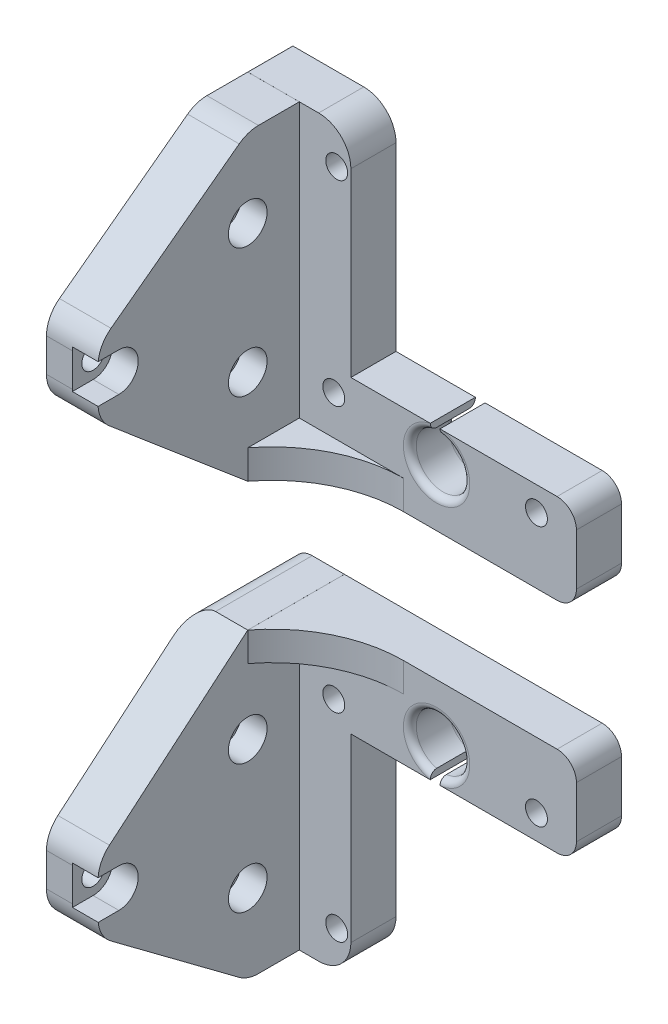
SolidWorks part; units mm, degrees
material "ABS"
ref_plane "Front Plane" through (0, 0, 0) normal (0, 0, 1) x (1, 0, 0)
ref_plane "Top Plane" through (0, 0, 0) normal (0, 1, 0) x (1, 0, 0)
ref_plane "Right Plane" through (0, 0, 0) normal (1, 0, 0) x (0, 0, -1)
ref_plane "Plane5" through (60, 0, 0) normal (1, 0, 0) x (0, 0, -1)
sketch "Sketch50" plane through (60, 0, 0) normal (1, 0, 0) x (0, 0, -1)
  line L0 (-38.2349, -28) -> (-38.2349, -38)
  line L1 (0, -55.3249) -> (-15, -55.3249)
  line L2 (0, -8.3249) -> (-15, -8.3249)
  line L4 (0, -55.3249) -> (0, -8.3249)
  line L5 (-15, -2.0171) -> (-15, -57.8143) construction
  line L9 (-38.2349, -28) -> (-15, -8.3249)
  line L10 (-38.2349, -38) -> (-15, -55.3249)
  circle A0 centre (-35, -33) radius 1.75
  circle A1 centre (-15, -23) radius 1.75
  circle A2 centre (-15, -43) radius 1.75
  dimension "D1" = 3.5
  dimension "D2" = 3.5
  dimension "D3" = 3.5
  dimension "D4" = 20
  dimension "D5" = 20
  dimension "D6" = 47
  dimension "D7" = 15
  dimension "D8" = 10
extrude "Extrude1" add sketch "Sketch50" along normal blind 8 separate body
sketch "Sketch52" plane through (0, 0, 0) normal (0, 0, -1) x (-1, 0, 0)
  line L0 (-60.0211, -55.3284) -> (-60.0211, -8.3284)
  line L1 (-111, -8.3284) -> (-111, -22.2806)
  line L2 (-60.0211, -8.3284) -> (-111, -8.3284)
  line L3 (-76, -22.2806) -> (-111, -22.2806)
  line L4 (-60.0211, -55.3284) -> (-76, -55.3284)
  line L5 (-76, -55.3249) -> (-76, -8.3249)
  line L6 (-76, -55.3284) -> (-76, -22.2806)
  circle A0 centre (-89.3, -17.2) radius 4.15
  circle A1 centre (-73.3515, -18.9313) radius 1.7
  circle A2 centre (-104.8, -18.5) radius 1.7
  circle A3 centre (-73.8015, -49.5086) radius 1.7
  point P3 (-113, -87.5802)
  point P9 (-74.0211, -54.9585)
  point P10 (-74.0211, -7.7617)
  dimension "D2" = 47
  dimension "D4" = 3.4
  dimension "D3" = 8.3
  dimension "D1" = 8
extrude "Extrude2" add sketch "Sketch52" against normal blind 7
fillet "Fillet1" radius 3 2 edges at (111, -22.2806, 3.5) (111, -8.3284, 3.5)
fillet "Fillet2" radius 5 1 edges at (76, -55.3284, 3.5)
sketch "Sketch54" plane through (0, -8.3284, 0) normal (0, 1, 0) x (1, 0, 0)
  line L0 (68, -7) -> (108, -7) construction
  line L1 (68, -15) -> (68, -7)
  line L2 (68, -15) -> (68, -38.2349) construction
  line L3 (68, 0) -> (68, -15) construction
  line L4 (68, -7) -> (84.1795, -7)
  arc A0 (84.1795, -7) -> (68, -15) centre (84.1795, -27.3609) ccw
extrude "Extrude3" add sketch "Sketch54" against normal blind 4.5
fillet "Fillet4" radius 5 3 edges at (64, -28, 38.2349) (64, -38, 38.2349) (64, -55.3249, 15)
fillet "Fillet5" radius 3 1 edges at (60, -8.3249, 7.5)
sketch "Sketch55" plane through (68, 0, 0) normal (1, 0, 0) x (0, 0, -1)
  line L0 (-35, -30) -> (-38.7879, -30)
  line L1 (-38.7879, -30) -> (-38.7879, -36)
  line L2 (-35, -36) -> (-38.7879, -36)
  arc A0 (-35, -36) -> (-35, -30) centre (-35, -33) ccw
  circle A1 centre (-15, -23) radius 3
  circle A2 centre (-15, -43) radius 3
  dimension "D1" = 6
  dimension "D2" = 6
  dimension "D3" = 6
extrude "Cut-Extrude3" cut sketch "Sketch55" against normal blind 4
sketch "Sketch56" plane through (0, 0, 0) normal (0, 0, -1) x (-1, 0, 0)
  line L0 (-108, -22.2806) -> (-76, -22.2806) construction
  line L1 (-89.3173, -23.6005) -> (-88.3204, -23.6005)
  line L2 (-89.3173, -23.6005) -> (-89.3173, -20.9607)
  line L3 (-89.3173, -20.9607) -> (-88.3204, -20.9607)
  line L4 (-88.3204, -23.6005) -> (-88.3204, -20.9607)
  line L5 (-89.3173, -23.6005) -> (-88.3204, -20.9607) construction
  line L6 (-89.3173, -20.9607) -> (-88.3204, -23.6005) construction
  point P0 (-88.8189, -22.2806)
fillet "Fillet9" radius 1 1 edges at (89.3, -13.05, 0)
fillet "Fillet10" radius 1 1 edges at (89.3, -13.05, 7)
sketch "Sketch57" plane through (0, -22.2806, 0) normal (0, -1, 0) x (1, 0, 0)
  line L0 (88.8276, 7.5275) -> (89.8276, 7.5275)
  line L2 (89.8276, -0.6284) -> (89.8276, 7.5275)
  line L3 (88.8276, -0.6284) -> (88.8276, 7.5275)
  line L4 (88.8276, -0.6284) -> (89.8276, -0.6284)
extrude "Extrude4" cut sketch "Sketch57" against normal blind 4
ref_plane "Plane6" through (0, 1.6716, 0) normal (0, 1, 0) x (1, 0, 0)
extrude "Cut-Extrude4" cut sketch "Sketch56" against normal up to surface (7 mm away) up to face at (84.4186, -28.299, 7)
mirror "Mirror1" about plane through (0, 1.6716, 0) normal (0, 1, 0) of bodies 133
